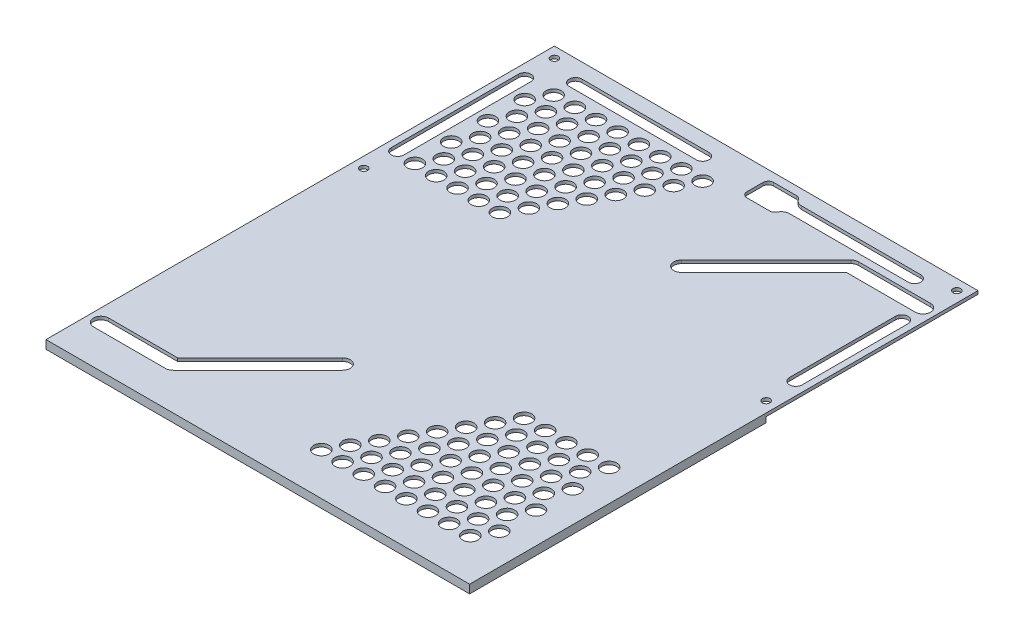
SolidWorks part; units mm, degrees
ref_plane "Front" through (0, 0, 0) normal (0, 0, 1) x (1, 0, 0)
ref_plane "Top" through (0, 0, 0) normal (0, 1, 0) x (1, 0, 0)
ref_plane "Right" through (0, 0, 0) normal (1, 0, 0) x (0, 0, -1)
sketch "Sketch1" plane through (0, 0, 0) normal (0, 1, 0) x (1, 0, 0)
  line L1 (0, 0) -> (127, 0)
  line L2 (0, 0) -> (0, 152.4)
  line L3 (0, 152.4) -> (127, 152.4)
  line L4 (127, 0) -> (127, 152.4)
  dimension "D1" = 152.4
  dimension "D2" = 127
extrude "Boss-Extrude1" add sketch "Sketch1" along normal blind 2.54
sketch "Sketch2" plane through (0, 2.54, 0) normal (0, 1, 0) x (1, 0, 0)
  line L0 (63.5, 152.4) -> (63.5, 0) construction
  line L1 (127, 152.4) -> (0, 152.4) construction
  line L2 (0, 0) -> (127, 0) construction
  line L3 (127, 76.2) -> (0, 76.2) construction
  line L4 (127, 0) -> (127, 152.4) construction
  line L5 (0, 152.4) -> (0, 0) construction
  circle A0 centre (63.5, 95.25) radius 1.016
  circle A1 centre (66.04, 95.25) radius 1.016
  circle A2 centre (68.58, 95.25) radius 1.016
  circle A3 centre (71.12, 95.25) radius 1.016
  circle A4 centre (73.66, 95.25) radius 1.016
  circle A5 centre (60.96, 95.25) radius 1.016
  circle A6 centre (58.42, 95.25) radius 1.016
  circle A7 centre (55.88, 95.25) radius 1.016
  circle A8 centre (53.34, 95.25) radius 1.016
  point P14 (63.5, 76.2)
  dimension "D1" = 2.032
  dimension "D4" = 57.15
  dimension "D2" = 5
  dimension "D3" = 5
sketch "Sketch5" plane through (0, 0, 0) normal (0, 1, 0) x (1, 0, 0)
  line L0 (63.5, 152.4) -> (63.5, 0) construction
  line L1 (0, 88.9) -> (127, 88.9)
  line L2 (0, 88.9) -> (0, 152.4)
  line L3 (0, 152.4) -> (127, 152.4)
  line L4 (127, 88.9) -> (127, 152.4)
  line L5 (0, 88.9) -> (127, 152.4) construction
  line L6 (0, 152.4) -> (127, 88.9) construction
  line L7 (127, 152.4) -> (0, 152.4) construction
  point P0 (63.5, 120.65)
  dimension "D1" = 63.5
  dimension "D2" = 127
extrude "Cut-Extrude2" cut sketch "Sketch5" along normal blind 1.5875
sketch "Sketch9" plane through (0, 2.54, 0) normal (0, 1, 0) x (1, 0, 0)
  line L0 (50.8, 38.1) -> (25.4, 12.7) construction
  line L1 (52.4164, 36.4836) -> (27.0164, 11.0836)
  line L2 (49.1836, 39.7164) -> (23.7836, 14.3164)
  line L3 (25.4, 12.7) -> (3.81, 12.7) construction
  line L4 (25.4, 10.414) -> (3.81, 10.414)
  line L5 (25.4, 14.986) -> (3.81, 14.986)
  line L6 (63.5, 152.4) -> (63.5, 0) construction
  line L7 (127, 76.2) -> (0, 76.2) construction
  line L8 (76.2, 114.3) -> (101.6, 139.7) construction
  line L9 (74.5836, 115.9164) -> (99.9836, 141.3164)
  line L10 (77.8164, 112.6836) -> (103.2164, 138.0836)
  line L11 (101.6, 139.7) -> (123.19, 139.7) construction
  line L12 (101.6, 141.986) -> (123.19, 141.986)
  line L13 (101.6, 137.414) -> (123.19, 137.414)
  arc A0 (52.4164, 36.4836) -> (49.1836, 39.7164) centre (50.8, 38.1) ccw
  arc A1 (23.7836, 14.3164) -> (27.0164, 11.0836) centre (25.4, 12.7) ccw
  arc A2 (25.4, 10.414) -> (25.4, 14.986) centre (25.4, 12.7) ccw
  arc A3 (3.81, 14.986) -> (3.81, 10.414) centre (3.81, 12.7) ccw
  arc A4 (74.5836, 115.9164) -> (77.8164, 112.6836) centre (76.2, 114.3) ccw
  arc A5 (103.2164, 138.0836) -> (99.9836, 141.3164) centre (101.6, 139.7) ccw
  arc A6 (101.6, 141.986) -> (101.6, 137.414) centre (101.6, 139.7) ccw
  arc A7 (123.19, 137.414) -> (123.19, 141.986) centre (123.19, 139.7) ccw
  point P2 (38.1, 25.4)
  point P7 (14.605, 12.7)
  point P23 (88.9, 127)
  point P28 (112.395, 139.7)
  point P35 (63.5, 76.2)
  dimension "D1" = 2.286
  dimension "D2" = 2.286
  dimension "D3" = 12.7
  dimension "D4" = 38.1
  dimension "D5" = 38.1
  dimension "D6" = 63.5
  dimension "D7" = 59.69
  dimension "D8" = 2
extrude "Cut-Extrude5" cut sketch "Sketch9" against normal through all contours A6 L9 A4 L10 L13 | A5 A6 L13 L10 | L13 A7 L12 A5 L10 | A2 L1 A0 L2 L5 | A1 A2 L5 L2 | L5 A3 L4 A1 L2 region at (39.3797, 2.54, -26.6777) region at (25.3939, 2.54, -12.7146) region at (12.7962, 2.54, -12.6976) region at (87.6203, 2.54, -125.7223) region at (101.6061, 2.54, -139.6854) region at (114.2038, 2.54, -139.7024)
sketch "Sketch10" plane through (0, 2.54, 0) normal (0, 1, 0) x (1, 0, 0)
  line L0 (127, 76.2) -> (0, 76.2) construction
  line L1 (63.5, 152.4) -> (63.5, 0) construction
  circle A1 centre (82.55, 12.7) radius 2.286
  circle A2 centre (85.7277, 18.2039) radius 2.286
  circle A3 centre (88.9053, 23.7078) radius 2.286
  circle A4 centre (92.083, 29.2117) radius 2.286
  circle A5 centre (95.2607, 34.7156) radius 2.286
  circle A6 centre (98.4384, 40.2195) radius 2.286
  circle A7 centre (101.616, 45.7234) radius 2.286
  circle A8 centre (104.7937, 51.2273) radius 2.286
  circle A9 centre (92.1245, 18.2039) radius 2.286
  circle A10 centre (95.3021, 23.7078) radius 2.286
  circle A11 centre (98.4798, 29.2117) radius 2.286
  circle A12 centre (101.6575, 34.7156) radius 2.286
  circle A13 centre (104.8352, 40.2195) radius 2.286
  circle A14 centre (108.0128, 45.7234) radius 2.286
  circle A15 centre (111.1905, 51.2273) radius 2.286
  circle A16 centre (88.9468, 12.7) radius 2.286
  circle A17 centre (98.5212, 18.2039) radius 2.286
  circle A18 centre (101.6989, 23.7078) radius 2.286
  circle A19 centre (104.8766, 29.2117) radius 2.286
  circle A20 centre (108.0543, 34.7156) radius 2.286
  circle A21 centre (111.2319, 40.2195) radius 2.286
  circle A22 centre (114.4096, 45.7234) radius 2.286
  circle A23 centre (117.5873, 51.2273) radius 2.286
  circle A24 centre (95.3436, 12.7) radius 2.286
  circle A25 centre (101.8105, 12.7) radius 2.286
  circle A26 centre (104.9882, 18.2039) radius 2.286
  circle A27 centre (108.1659, 23.7078) radius 2.286
  circle A28 centre (111.3436, 29.2117) radius 2.286
  circle A29 centre (114.5212, 34.7156) radius 2.286
  circle A30 centre (117.6989, 40.2195) radius 2.286
  circle A31 centre (108.1605, 12.7) radius 2.286
  circle A32 centre (111.3382, 18.2039) radius 2.286
  circle A33 centre (114.5159, 23.7078) radius 2.286
  circle A34 centre (117.6936, 29.2117) radius 2.286
  circle A35 centre (114.5105, 12.7) radius 2.286
  circle A36 centre (117.6882, 18.2039) radius 2.286
  circle A37 centre (44.582, 139.5661) radius 2.286
  circle A38 centre (41.4043, 134.0622) radius 2.286
  circle A39 centre (38.2266, 128.5583) radius 2.286
  circle A40 centre (35.0489, 123.0544) radius 2.286
  circle A41 centre (31.8713, 117.5505) radius 2.286
  circle A42 centre (28.6936, 112.0466) radius 2.286
  circle A43 centre (25.5159, 106.5427) radius 2.286
  circle A44 centre (22.3382, 101.0388) radius 2.286
  circle A45 centre (35.0075, 134.0622) radius 2.286
  circle A46 centre (31.8298, 128.5583) radius 2.286
  circle A47 centre (28.6522, 123.0544) radius 2.286
  circle A48 centre (25.4745, 117.5505) radius 2.286
  circle A49 centre (22.2968, 112.0466) radius 2.286
  circle A50 centre (19.1191, 106.5427) radius 2.286
  circle A51 centre (15.9415, 101.0388) radius 2.286
  circle A52 centre (38.1852, 139.5661) radius 2.286
  circle A53 centre (28.6107, 134.0622) radius 2.286
  circle A54 centre (25.433, 128.5583) radius 2.286
  circle A55 centre (22.2554, 123.0544) radius 2.286
  circle A56 centre (19.0777, 117.5505) radius 2.286
  circle A57 centre (15.9, 112.0466) radius 2.286
  circle A58 centre (12.7223, 106.5427) radius 2.286
  circle A59 centre (9.5447, 101.0388) radius 2.286
  circle A60 centre (31.7884, 139.5661) radius 2.286
  circle A61 centre (25.3214, 139.5661) radius 2.286
  circle A62 centre (22.1438, 134.0622) radius 2.286
  circle A63 centre (18.9661, 128.5583) radius 2.286
  circle A64 centre (15.7884, 123.0544) radius 2.286
  circle A65 centre (12.6107, 117.5505) radius 2.286
  circle A66 centre (9.4331, 112.0466) radius 2.286
  circle A67 centre (18.9714, 139.5661) radius 2.286
  circle A68 centre (15.7938, 134.0622) radius 2.286
  circle A69 centre (12.6161, 128.5583) radius 2.286
  circle A70 centre (9.4384, 123.0544) radius 2.286
  circle A71 centre (12.6214, 139.5661) radius 2.286
  circle A72 centre (9.4438, 134.0622) radius 2.286
  circle A73 centre (76.2, 12.7) radius 2.286
  circle A74 centre (79.3777, 18.2039) radius 2.286
  circle A75 centre (82.5553, 23.7078) radius 2.286
  circle A76 centre (85.733, 29.2117) radius 2.286
  circle A77 centre (88.9107, 34.7156) radius 2.286
  circle A78 centre (92.0884, 40.2195) radius 2.286
  circle A79 centre (95.266, 45.7234) radius 2.286
  circle A80 centre (98.4437, 51.2273) radius 2.286
  circle A81 centre (69.85, 12.7) radius 2.286
  circle A82 centre (73.0277, 18.2039) radius 2.286
  circle A83 centre (76.2053, 23.7078) radius 2.286
  circle A84 centre (79.383, 29.2117) radius 2.286
  circle A85 centre (82.5607, 34.7156) radius 2.286
  circle A86 centre (85.7384, 40.2195) radius 2.286
  circle A87 centre (88.916, 45.7234) radius 2.286
  circle A88 centre (92.0937, 51.2273) radius 2.286
  circle A89 centre (28.6882, 101.0388) radius 2.286
  circle A90 centre (31.8659, 106.5427) radius 2.286
  circle A91 centre (35.0436, 112.0466) radius 2.286
  circle A92 centre (38.2213, 117.5505) radius 2.286
  circle A93 centre (41.3989, 123.0544) radius 2.286
  circle A94 centre (44.5766, 128.5583) radius 2.286
  circle A95 centre (47.7543, 134.0622) radius 2.286
  circle A96 centre (50.932, 139.5661) radius 2.286
  circle A97 centre (35.0382, 101.0388) radius 2.286
  circle A98 centre (38.2159, 106.5427) radius 2.286
  circle A99 centre (41.3936, 112.0466) radius 2.286
  circle A100 centre (44.5713, 117.5505) radius 2.286
  circle A101 centre (47.7489, 123.0544) radius 2.286
  circle A102 centre (50.9266, 128.5583) radius 2.286
  circle A103 centre (54.1043, 134.0622) radius 2.286
  circle A104 centre (57.282, 139.5661) radius 2.286
  point P151 (63.566, 76.133)
  dimension "D1" = 3
  dimension "D3" = 2
  dimension "D4" = 4.572
  dimension "D5" = 63.5
  dimension "D6" = 19.05
  dimension "D2" = 2
  dimension "D7" = 8
  dimension "D8" = 2
  dimension "D10" = 3
  dimension "D11" = 3
  dimension "D9" = 2
extrude "Cut-Extrude6" cut sketch "Sketch10" against normal through all
sketch "Sketch12" plane through (0, 2.54, 0) normal (0, 1, 0) x (1, 0, 0)
  line L0 (76.2, 146.05) -> (114.3, 146.05) construction
  line L1 (76.2, 147.955) -> (114.3, 147.955)
  line L2 (76.2, 144.145) -> (114.3, 144.145)
  line L3 (63.5, 152.4) -> (63.5, 0) construction
  line L4 (63.5, 152.4) -> (63.5, 135.3884) construction
  line L5 (50.8, 146.05) -> (12.7, 146.05) construction
  line L6 (50.8, 147.955) -> (12.7, 147.955)
  line L7 (50.8, 144.145) -> (12.7, 144.145)
  line L8 (3.81, 139.7) -> (3.81, 101.6) construction
  line L9 (5.715, 139.7) -> (5.715, 101.6)
  line L10 (1.905, 139.7) -> (1.905, 101.6)
  line L11 (127, 152.4) -> (0, 152.4) construction
  arc A0 (76.2, 147.955) -> (76.2, 144.145) centre (76.2, 146.05) ccw
  arc A1 (114.3, 144.145) -> (114.3, 147.955) centre (114.3, 146.05) ccw
  arc A2 (50.8, 147.955) -> (50.8, 144.145) centre (50.8, 146.05) cw
  arc A3 (12.7, 144.145) -> (12.7, 147.955) centre (12.7, 146.05) cw
  arc A4 (5.715, 139.7) -> (1.905, 139.7) centre (3.81, 139.7) ccw
  arc A5 (1.905, 101.6) -> (5.715, 101.6) centre (3.81, 101.6) ccw
  point P2 (95.25, 146.05)
  point P14 (31.75, 146.05)
  point P21 (3.81, 120.65)
  dimension "D1" = 3.81
  dimension "D2" = 38.1
  dimension "D3" = 50.8
  dimension "D4" = 3.81
  dimension "D5" = 12.7
  dimension "D6" = 38.1
  dimension "D7" = 59.69
  dimension "D8" = 6.35
extrude "Cut-Extrude7" cut sketch "Sketch12" against normal through all and the other way through all
sketch "Sketch13" plane through (0, 0, 0) normal (0, -1, 0) x (1, 0, 0)
  line L0 (52.4164, -39.7164) -> (14.4021, -1.7021) construction
  line L1 (1.524, -12.7) -> (44.6383, -12.7) construction
  line L2 (49.1836, -39.7164) -> (52.4164, -36.4836) construction
  line L3 (3.81, -14.986) -> (3.81, -10.414) construction
  line L4 (50.8, -38.1) -> (25.4, -12.7) construction
  line L5 (47.4324, -41.4676) -> (22.0324, -16.0676)
  line L6 (54.1676, -34.7324) -> (28.7676, -9.3324)
  line L7 (25.4, -12.7) -> (3.81, -12.7) construction
  line L8 (25.4, -17.4625) -> (3.81, -17.4625)
  line L9 (25.4, -7.9375) -> (3.81, -7.9375)
  arc A0 (49.1836, -39.7164) -> (52.4164, -36.4836) centre (50.8, -38.1) ccw construction
  arc A1 (3.81, -10.414) -> (3.81, -14.986) centre (3.81, -12.7) ccw construction
  arc A2 (47.4324, -41.4676) -> (54.1676, -34.7324) centre (50.8, -38.1) ccw
  arc A3 (28.7676, -9.3324) -> (22.0324, -16.0676) centre (25.4, -12.7) ccw
  arc A4 (25.4, -17.4625) -> (25.4, -7.9375) centre (25.4, -12.7) ccw
  arc A5 (3.81, -7.9375) -> (3.81, -17.4625) centre (3.81, -12.7) ccw
  point P18 (25.4, -12.7)
  point P21 (38.1, -25.4)
  point P28 (14.605, -12.7)
  dimension "D1" = 9.525
  dimension "D2" = 9.525
extrude "Cut-Extrude8" cut sketch "Sketch13" against normal blind 1.5875 contours A4 L8 L5 A2 L6 | L8 A4 A3 L5 | L9 A5 L8 L5 A3 region at (40.7695, 0, -28.0604) region at (10.8344, 0, -12.6894) region at (25.3874, 0, -12.7304)
sketch "Sketch14" plane through (0, 0, 0) normal (0, -1, 0) x (1, 0, 0)
  line L0 (117.5873, -48.9413) -> (117.5873, -53.5133) construction
  line L1 (117.5873, -53.5133) -> (119.8733, -51.2273) construction
  line L2 (119.8733, -51.2273) -> (115.3013, -51.2273) construction
  line L3 (87.9693, -53.6085) -> (65.7256, -15.0812)
  line L4 (69.85, -7.9375) -> (114.5105, -7.9375)
  line L5 (92.0937, -55.9898) -> (117.5873, -55.9898)
  line L6 (118.683, -10.404) -> (121.5009, -15.35)
  line L7 (122.3498, -51.2418) -> (122.4507, -18.2184)
  circle A0 centre (69.85, -12.7) radius 4.7625
  circle A1 centre (92.0937, -51.2273) radius 4.7625
  circle A2 centre (114.5105, -12.7) radius 4.7625
  circle A3 centre (117.5873, -51.2273) radius 2.286 construction
  circle A4 centre (117.5873, -51.2273) radius 4.7625
  circle A5 centre (117.6882, -18.2039) radius 4.7625
  dimension "D1" = 9.525
  dimension "D2" = 9.525
  dimension "D3" = 9.525
  dimension "D4" = 9.525
  dimension "D5" = 9.525
extrude "Cut-Extrude9" cut sketch "Sketch14" against normal blind 1.5875 contours A5 A2 L4 A0 L3 A1 L5 A4 L7 | A0 | A5 A2 | A5 A2 | A4 | A1 | A2 A5 | A5 L6 A2 region at (97.5263, 0, -29.8912) region at (92.0937, 0, -51.2273) region at (69.85, 0, -12.7) region at (117.5873, 0, -51.2273) region at (114.0661, 0, -11.9303) region at (119.8852, 0, -13.2252) region at (116.0994, 0, -15.4519) region at (118.1326, 0, -18.9736)
sketch "Sketch15" plane through (0, 2.54, 0) normal (0, 1, 0) x (1, 0, 0)
  line L0 (127, 152.4) -> (0, 152.4) construction
  line L1 (0, 152.4) -> (0, 0) construction
  line L2 (63.5, 152.4) -> (63.5, 127.0009) construction
  circle A0 centre (3.175, 149.225) radius 1.1303
  circle A1 centre (3.175, 92.075) radius 1.1303
  circle A2 centre (123.825, 92.075) radius 1.1303
  circle A3 centre (123.825, 149.225) radius 1.1303
  dimension "D1" = 2.2606
  dimension "D2" = 3.175
  dimension "D3" = 3.175
  dimension "D4" = 2
extrude "Cut-Extrude10" cut sketch "Sketch15" against normal through all
sketch "Sketch16" plane through (0, 2.54, 0) normal (0, 1, 0) x (1, 0, 0)
  line L0 (123.19, 101.6) -> (123.19, 133.35) construction
  line L1 (121.285, 101.6) -> (121.285, 133.35)
  line L2 (125.095, 101.6) -> (125.095, 133.35)
  line L3 (63.5, 152.4) -> (63.5, 0) construction
  line L4 (127, 152.4) -> (0, 152.4) construction
  arc A0 (121.285, 101.6) -> (125.095, 101.6) centre (123.19, 101.6) ccw
  arc A1 (125.095, 133.35) -> (121.285, 133.35) centre (123.19, 133.35) ccw
  point P2 (123.19, 117.475)
  dimension "D1" = 1.905
  dimension "D2" = 59.69
  dimension "D3" = 31.75
  dimension "D4" = 19.05
extrude "Cut-Extrude11" cut sketch "Sketch16" against normal through all
sketch "Sketch17" plane through (0, 2.54, 0) normal (0, 1, 0) x (1, 0, 0)
  line L0 (127, 152.4) -> (0, 152.4) construction
  line L1 (75.0875, 149.86) -> (68.2625, 149.86)
  line L2 (76.675, 148.2725) -> (76.675, 143.4475)
  line L3 (75.0875, 141.86) -> (68.2625, 141.86)
  line L4 (66.675, 148.2725) -> (66.675, 143.4475)
  line L5 (63.5, 152.4) -> (63.5, 0) construction
  arc A0 (75.0875, 149.86) -> (76.675, 148.2725) centre (75.0875, 148.2725) cw
  arc A1 (76.675, 143.4475) -> (75.0875, 141.86) centre (75.0875, 143.4475) cw
  arc A2 (68.2625, 141.86) -> (66.675, 143.4475) centre (68.2625, 143.4475) cw
  arc A3 (68.2625, 149.86) -> (66.675, 148.2725) centre (68.2625, 148.2725) ccw
  point P10 (76.675, 149.86)
  point P15 (66.675, 141.86)
  point P18 (66.675, 149.86)
  dimension "D5" = 1.5875
  dimension "D1" = 8
  dimension "D2" = 10
  dimension "D3" = 2.54
  dimension "D4" = 3.175
extrude "Cut-Extrude12" cut sketch "Sketch17" against normal through all
fillet "Fillet1" radius 2.54 2 edges at (76.675, 2.0638, -147.955) (76.675, 2.0638, -144.145)
